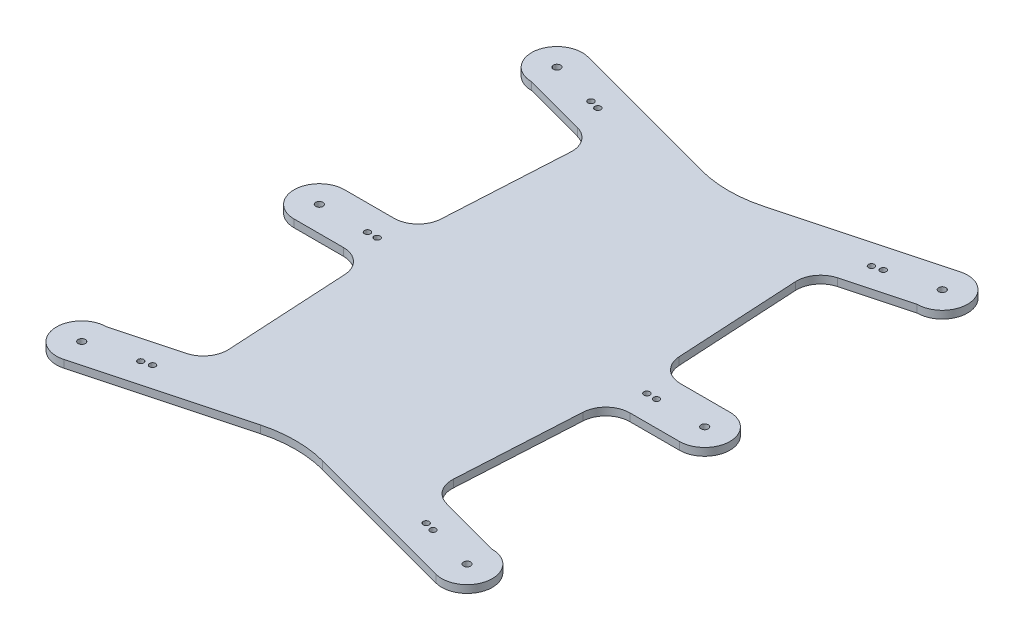
SolidWorks part; units mm, degrees
ref_plane "Front Plane" through (0, 0, 0) normal (0, 0, 1) x (1, 0, 0)
ref_plane "Top Plane" through (0, 0, 0) normal (0, 1, 0) x (1, 0, 0)
ref_plane "Right Plane" through (0, 0, 0) normal (1, 0, 0) x (0, 0, -1)
sketch "Sketch1" plane through (0, 0, 0) normal (0, 1, 0) x (1, 0, 0)
  line L0 (0, 32.1883) -> (0, -21.4181) construction
  line L1 (0, 0) -> (27.1703, 0) construction
  line L2 (-80, 10.5) -> (-50, 10.5)
  line L3 (-50, 10.5) -> (-46.1926, 79.0959)
  line L4 (-46.1926, 79.0959) -> (-80, 88.1546)
  line L5 (-77.2824, 108.7968) -> (0, 88.0891)
  line L6 (77.2824, 108.7968) -> (0, 88.0891)
  line L7 (46.1926, 79.0959) -> (80, 88.1546)
  line L8 (50, 10.5) -> (46.1926, 79.0959)
  line L9 (80, 10.5) -> (50, 10.5)
  line L10 (80, -10.5) -> (50, -10.5)
  line L11 (50, -10.5) -> (46.1926, -79.0959)
  line L12 (46.1926, -79.0959) -> (80, -88.1546)
  line L13 (77.2824, -108.7968) -> (0, -88.0891)
  line L14 (-77.2824, -108.7968) -> (0, -88.0891)
  line L15 (-46.1926, -79.0959) -> (-80, -88.1546)
  line L16 (-50, -10.5) -> (-46.1926, -79.0959)
  line L17 (-80, -10.5) -> (-50, -10.5)
  arc A0 (-80, 10.5) -> (-80, -10.5) centre (-80, 0) ccw
  arc A1 (-77.2824, 108.7968) -> (-80, 88.1546) centre (-80, 98.6546) ccw
  circle A2 centre (-80, 98.6546) radius 1.5
  circle A3 centre (-80, 0) radius 1.5
  circle A4 centre (80, 0) radius 1.5
  circle A5 centre (80, 98.6546) radius 1.5
  arc A6 (77.2824, 108.7968) -> (80, 88.1546) centre (80, 98.6546) cw
  arc A7 (80, 10.5) -> (80, -10.5) centre (80, 0) cw
  arc A8 (77.2824, -108.7968) -> (80, -88.1546) centre (80, -98.6546) ccw
  circle A9 centre (80, -98.6546) radius 1.5
  circle A10 centre (-80, -98.6546) radius 1.5
  arc A11 (-77.2824, -108.7968) -> (-80, -88.1546) centre (-80, -98.6546) cw
  dimension "D2" = 10.5
  dimension "D3" = 3
  dimension "D1" = 75
  dimension "D4" = 80
  dimension "D5" = 30
  dimension "D6" = 35
  dimension "D7" = 68.5959
extrude "Boss-Extrude1" add sketch "Sketch1" along normal blind 3.175
sketch "Sketch2" plane through (0, 3.175, 0) normal (0, 1, 0) x (1, 0, 0)
  arc A0 (55.6104, -92.1194) -> (58.0252, -92.7665) centre (56.8178, -92.4429) ccw construction
  arc A1 (58.0252, -92.7665) -> (55.6104, -92.1194) centre (56.8178, -92.4429) ccw construction
  arc A2 (61.8889, -93.8017) -> (59.4741, -93.1547) centre (60.6815, -93.4782) ccw construction
  arc A3 (59.4741, -93.1547) -> (61.8889, -93.8017) centre (60.6815, -93.4782) ccw construction
  arc A4 (54.75, 0) -> (57.25, 0) centre (56, 0) ccw construction
  arc A5 (57.25, 0) -> (54.75, 0) centre (56, 0) ccw construction
  arc A6 (61.25, 0) -> (58.75, 0) centre (60, 0) ccw construction
  arc A7 (58.75, 0) -> (61.25, 0) centre (60, 0) ccw construction
  arc A8 (58.0252, 92.7665) -> (55.6104, 92.1194) centre (56.8178, 92.4429) ccw construction
  arc A9 (55.6104, 92.1194) -> (58.0252, 92.7665) centre (56.8178, 92.4429) ccw construction
  arc A10 (61.8889, 93.8017) -> (59.4741, 93.1547) centre (60.6815, 93.4782) ccw construction
  arc A11 (59.4741, 93.1547) -> (61.8889, 93.8017) centre (60.6815, 93.4782) ccw construction
  arc A12 (-59.4741, 93.1547) -> (-61.8889, 93.8017) centre (-60.6815, 93.4782) ccw construction
  arc A13 (-61.8889, 93.8017) -> (-59.4741, 93.1547) centre (-60.6815, 93.4782) ccw construction
  arc A14 (-58.0252, 92.7665) -> (-55.6104, 92.1194) centre (-56.8178, 92.4429) ccw construction
  arc A15 (-55.6104, 92.1194) -> (-58.0252, 92.7665) centre (-56.8178, 92.4429) ccw construction
  arc A16 (-58.75, 0) -> (-61.25, 0) centre (-60, 0) ccw construction
  arc A17 (-61.25, 0) -> (-58.75, 0) centre (-60, 0) ccw construction
  arc A18 (-57.25, 0) -> (-54.75, 0) centre (-56, 0) ccw construction
  arc A19 (-54.75, 0) -> (-57.25, 0) centre (-56, 0) ccw construction
  arc A20 (-58.0252, -92.7665) -> (-55.6104, -92.1194) centre (-56.8178, -92.4429) ccw construction
  arc A21 (-55.6104, -92.1194) -> (-58.0252, -92.7665) centre (-56.8178, -92.4429) ccw construction
  arc A22 (-59.4741, -93.1547) -> (-61.8889, -93.8017) centre (-60.6815, -93.4782) ccw construction
  arc A23 (-61.8889, -93.8017) -> (-59.4741, -93.1547) centre (-60.6815, -93.4782) ccw construction
  arc A24 (55.6104, -92.1194) -> (58.0252, -92.7665) centre (56.8178, -92.4429) ccw
  arc A25 (58.0252, -92.7665) -> (55.6104, -92.1194) centre (56.8178, -92.4429) ccw
  arc A26 (61.8889, -93.8017) -> (59.4741, -93.1547) centre (60.6815, -93.4782) ccw
  arc A27 (59.4741, -93.1547) -> (61.8889, -93.8017) centre (60.6815, -93.4782) ccw
  arc A28 (54.75, 0) -> (57.25, 0) centre (56, 0) ccw
  arc A29 (57.25, 0) -> (54.75, 0) centre (56, 0) ccw
  arc A30 (61.25, 0) -> (58.75, 0) centre (60, 0) ccw
  arc A31 (58.75, 0) -> (61.25, 0) centre (60, 0) ccw
  arc A32 (58.0252, 92.7665) -> (55.6104, 92.1194) centre (56.8178, 92.4429) ccw
  arc A33 (55.6104, 92.1194) -> (58.0252, 92.7665) centre (56.8178, 92.4429) ccw
  arc A34 (61.8889, 93.8017) -> (59.4741, 93.1547) centre (60.6815, 93.4782) ccw
  arc A35 (59.4741, 93.1547) -> (61.8889, 93.8017) centre (60.6815, 93.4782) ccw
  arc A36 (-59.4741, 93.1547) -> (-61.8889, 93.8017) centre (-60.6815, 93.4782) ccw
  arc A37 (-61.8889, 93.8017) -> (-59.4741, 93.1547) centre (-60.6815, 93.4782) ccw
  arc A38 (-58.0252, 92.7665) -> (-55.6104, 92.1194) centre (-56.8178, 92.4429) ccw
  arc A39 (-55.6104, 92.1194) -> (-58.0252, 92.7665) centre (-56.8178, 92.4429) ccw
  arc A40 (-58.75, 0) -> (-61.25, 0) centre (-60, 0) ccw
  arc A41 (-61.25, 0) -> (-58.75, 0) centre (-60, 0) ccw
  arc A42 (-57.25, 0) -> (-54.75, 0) centre (-56, 0) ccw
  arc A43 (-54.75, 0) -> (-57.25, 0) centre (-56, 0) ccw
  arc A44 (-58.0252, -92.7665) -> (-55.6104, -92.1194) centre (-56.8178, -92.4429) ccw
  arc A45 (-55.6104, -92.1194) -> (-58.0252, -92.7665) centre (-56.8178, -92.4429) ccw
  arc A46 (-59.4741, -93.1547) -> (-61.8889, -93.8017) centre (-60.6815, -93.4782) ccw
  arc A47 (-61.8889, -93.8017) -> (-59.4741, -93.1547) centre (-60.6815, -93.4782) ccw
extrude "Cut-Extrude1" cut sketch "Sketch2" against normal through all
fillet "Fillet1" radius 50 2 edges at (0, 1.5875, -88.0891) (0, 1.5875, 88.0891)
fillet "Fillet2" radius 10 8 edges at (46.1926, 1.5875, 79.0959) (50, 1.5875, 10.5) (50, 1.5875, -10.5) (46.1926, 1.5875, -79.0959) (-46.1926, 1.5875, -79.0959) (-50, 1.5875, -10.5) (-50, 1.5875, 10.5) (-46.1926, 1.5875, 79.0959)
